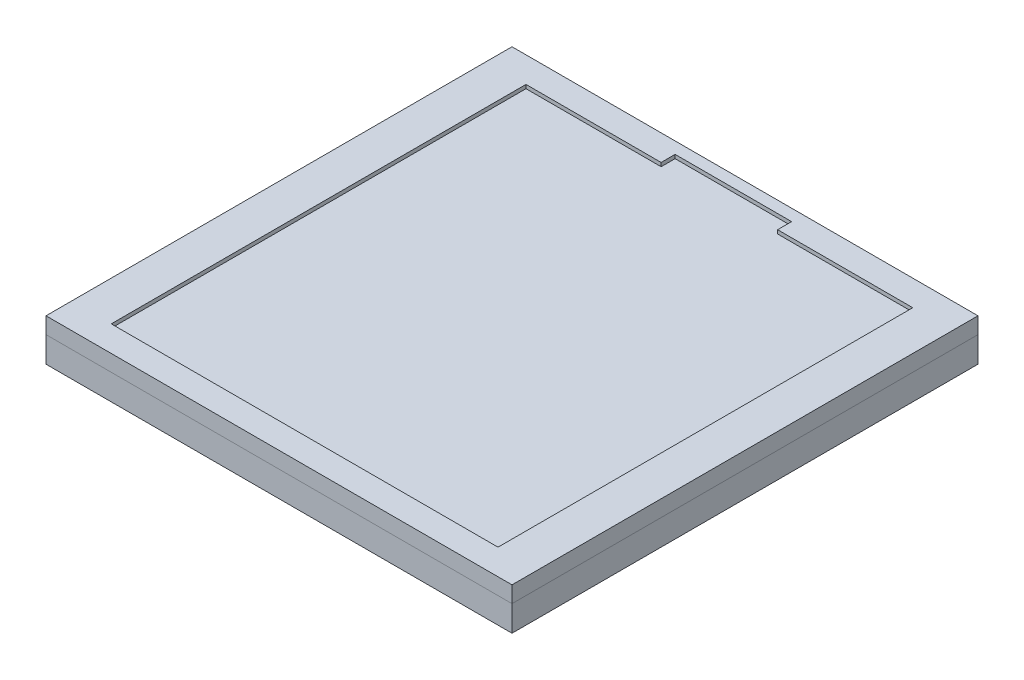
SolidWorks part; units mm, degrees
ref_plane "Спереди" through (0, 0, 0) normal (0, 0, 1) x (1, 0, 0)
ref_plane "Сверху" through (0, 0, 0) normal (0, 1, 0) x (1, 0, 0)
ref_plane "Справа" through (0, 0, 0) normal (1, 0, 0) x (0, 0, -1)
sketch "Эскиз1" plane through (0, 0, 0) normal (0, 1, 0) x (1, 0, 0)
  line L1 (0, 0) -> (1000, 0)
  line L2 (0, 0) -> (0, 1000)
  line L3 (0, 1000) -> (1000, 1000)
  line L4 (1000, 0) -> (1000, 1000)
  dimension "D1" = 1000
  dimension "D2" = 1000
extrude "Бобышка-Вытянуть1" add sketch "Эскиз1" along normal blind 35
sketch "Эскиз2" [suppressed] plane through (0, 30, 0) normal (0, 1, 0) x (-1, 0, 0)
  line L1 (-25, -875) -> (-875, -875)
  line L2 (-25, -875) -> (-25, -25)
  line L3 (-25, -25) -> (-875, -25)
  line L4 (-875, -875) -> (-875, -25)
  line L5 (-900, -900) -> (0, -900) construction
  line L8 (-875, -450) -> (-900, -450) construction
  line L9 (-900, 0) -> (-900, -900) construction
  line L10 (-450, -875) -> (-450, -900) construction
  dimension "D1" = 25
ref_plane "Плоскость1" [suppressed] through (0, 26, 0) normal (0, -1, 0) x (1, 0, 0)
sketch "Эскиз3" [suppressed] plane through (0, 26, 0) normal (0, 1, 0) x (-1, 0, 0)
  line L0 (0, -450) -> (-350, -450) construction
  line L1 (0, -900) -> (0, 0) construction
  line L3 (-290, -390) -> (-410, -390)
  line L4 (-290, -390) -> (-290, -510)
  line L5 (-290, -510) -> (-410, -510)
  line L6 (-410, -390) -> (-410, -510)
  line L7 (-290, -390) -> (-410, -510) construction
  line L8 (-290, -510) -> (-410, -390) construction
  dimension "D1" = 350
  dimension "D2" = 120
sketch3d "Трехмерный эскиз1" [suppressed]
  line L0 (25, 30, -875) -> (290, 26, -510)
  line L1 (410, 26, -510) -> (875, 30, -875)
  line L2 (410, 26, -390) -> (875, 30, -25)
  line L3 (25, 30, -25) -> (290, 26, -390)
loft "Вырез-По сечениям2" [suppressed] cut profiles "Эскиз2", "Эскиз3"
sketch "Эскиз5" [suppressed] plane through (0, 26, 0) normal (0, 1, 0) x (-1, 0, 0)
  line L0 (-290, -510) -> (-410, -390) construction
  circle A0 centre (-350, -450) radius 45
  dimension "D1" = 90
extrude "Вырез-Вытянуть4" [suppressed] cut sketch "Эскиз5" against normal through all
sketch "Эскиз6" plane through (0, 35, 0) normal (0, 1, 0) x (-1, 0, 0)
  line L0 (-85, -945) -> (-85, -55)
  line L1 (-85, -55) -> (-915, -55)
  line L2 (-915, -55) -> (-915, -945)
  line L3 (-915, -945) -> (-625, -945)
  line L4 (-625, -945) -> (-625, -975)
  line L5 (-625, -975) -> (-375, -975)
  line L6 (-375, -975) -> (-375, -945)
  line L7 (-375, -945) -> (-85, -945)
  line L8 (-1000, -1000) -> (0, -1000) construction
  line L10 (-85, -500) -> (0, -500) construction
  line L11 (0, -1000) -> (0, 0) construction
  line L12 (-375, -945) -> (-625, -945) construction
  line L13 (-500, -945) -> (-500, -1000) construction
  dimension "D1" = 85
  dimension "D2" = 250
  dimension "D3" = 55
  dimension "D4" = 30
extrude "Вырез-Вытянуть5" cut sketch "Эскиз6" against normal blind 8
sketch "Эскиз7" plane through (0, 0, 0) normal (0, -1, 0) x (-1, 0, 0)
  line L0 (-500, 0) -> (-500, 30) construction
  line L1 (0, 0) -> (-1000, 0)
  line L2 (0, 0) -> (0, 1000)
  line L3 (0, 1000) -> (-1000, 1000)
  line L4 (-1000, 0) -> (-1000, 1000)
  line L5 (-30, 30) -> (-970, 30)
  line L6 (-30, 30) -> (-30, 970)
  line L7 (-30, 970) -> (-970, 970)
  line L8 (-970, 30) -> (-970, 970)
  line L9 (0, 500) -> (-30, 500) construction
  dimension "D1" = 30
extrude "Бобышка-Вытянуть2" add sketch "Эскиз7" along normal offset from surface (55 mm away) 90 separate body up to face at (500, 35, -730)
